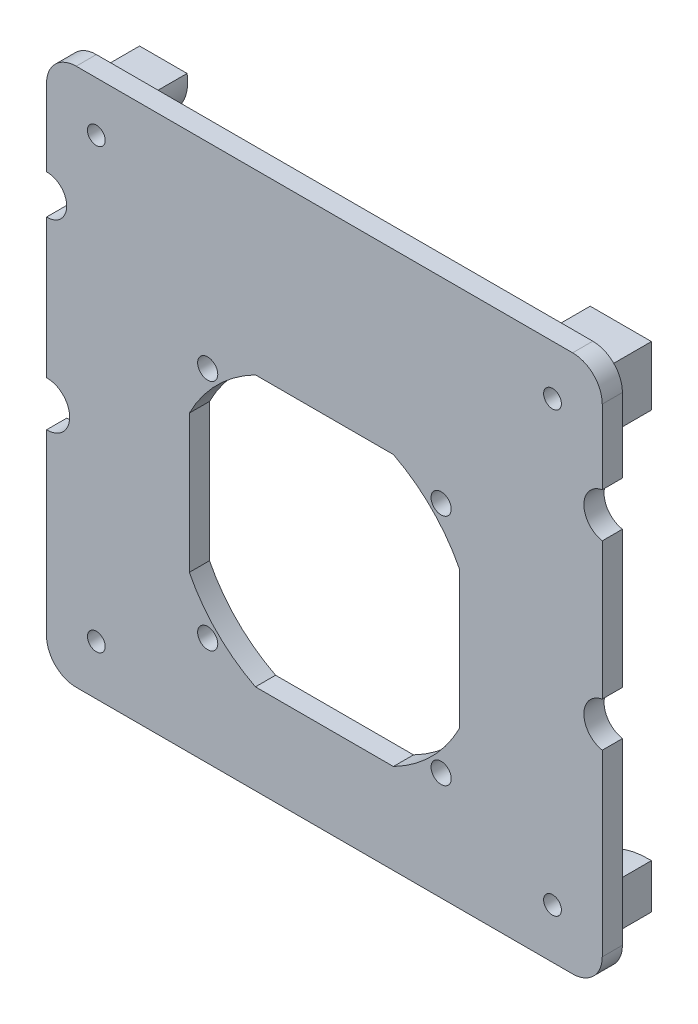
SolidWorks part; units mm, degrees
material "ABS"
ref_plane "Front Plane" through (0, 0, 0) normal (0, 0, 1) x (1, 0, 0)
ref_plane "Top Plane" through (0, 0, 0) normal (0, 1, 0) x (1, 0, 0)
ref_plane "Right Plane" through (0, 0, 0) normal (1, 0, 0) x (0, 0, -1)
sketch "Sketch1" plane through (0, 0, 0) normal (0, 0, 1) x (1, 0, 0)
  line L1 (94.3693, -146.4001) -> (-24.7567, -146.4001)
  line L2 (94.3693, -146.4001) -> (94.3693, -31.0841)
  line L3 (94.3693, -31.0841) -> (-24.7567, -31.0841)
  line L4 (-24.7567, -146.4001) -> (-24.7567, -31.0841)
  circle A0 centre (83.7013, -135.7321) radius 1.905
  circle A2 centre (83.7013, -135.7321) radius 2.54
  circle A3 centre (-14.0887, -135.7321) radius 1.905
  circle A4 centre (-14.0887, -135.7321) radius 2.54
  circle A5 centre (-14.0887, -41.7521) radius 1.905
  circle A6 centre (-14.0887, -41.7521) radius 2.54
  circle A7 centre (83.7013, -41.7521) radius 1.905
  circle A8 centre (83.7013, -41.7521) radius 2.54
extrude "Boss-Extrude1" add sketch "Sketch1" against normal up to surface (10.922 mm away) contours A8 A7 | A6 A5 | A4 A3 | A2 A0 region at (81.2332, -135.7321, 0) region at (-16.5568, -135.7321, 0) region at (-16.5568, -41.7521, 0) region at (81.2332, -41.7521, 0)
sketch "Sketch2" plane through (0, 0, 0) normal (0, 0, 1) x (1, 0, 0)
  line L0 (-6.8751, -142.0821) -> (-20.4387, -142.0821)
  line L1 (-20.4387, -142.0821) -> (-20.4387, -128.5961)
  line L2 (-20.4387, -142.0821) -> (-20.4387, -99.3264) construction
  line L3 (-6.8751, -141.7011) -> (-20.0577, -141.7011)
  line L4 (-20.0577, -141.7011) -> (-20.0577, -128.5961)
  line L5 (-20.4387, -46.0066) -> (-20.4387, -35.4021) construction
  line L6 (-20.4387, -46.0066) -> (-20.4387, -35.4021)
  line L8 (-20.4387, -35.4021) -> (-9.8742, -35.4021)
  line L9 (-20.4387, -35.4021) -> (6.7885, -35.4021) construction
  line L10 (-20.0577, -46.0066) -> (-20.0577, -35.7831)
  line L11 (-20.0577, -35.7831) -> (-9.8742, -35.7831)
  line L12 (73.9223, -142.0821) -> (90.0513, -142.0821)
  line L14 (90.0513, -132.1507) -> (90.0513, -142.0821)
  line L15 (73.9223, -141.7011) -> (89.6703, -141.7011)
  line L17 (90.0513, -48.5085) -> (90.0513, -35.4021)
  line L18 (90.0513, -35.4021) -> (76.5401, -35.4021)
  line L19 (89.6703, -48.5085) -> (89.6703, -35.7831)
  line L20 (89.6703, -35.7831) -> (76.5401, -35.7831)
  line L21 (89.6703, -132.1507) -> (89.6703, -141.7011)
  arc A0 (-6.8751, -141.7011) -> (-20.0577, -128.5961) centre (-30.9159, -152.7015) ccw
  arc A1 (-9.8742, -35.7831) -> (-20.0577, -46.0066) centre (-18.5276, -37.3471) cw
  arc A2 (89.6703, -48.5085) -> (76.5401, -35.7831) centre (98.2455, -26.5239) cw
  arc A6 (73.9223, -141.7011) -> (89.6703, -132.1507) centre (89.0742, -148.9266) cw
  circle A7 centre (83.7013, -135.7321) radius 2.54
  circle A8 centre (83.7013, -41.7521) radius 2.54
  circle A9 centre (-14.0887, -41.7521) radius 2.54
  circle A10 centre (-14.0887, -135.7321) radius 2.54
  circle A11 centre (-14.0887, -135.7321) radius 1.905
  circle A12 centre (83.7013, -135.7321) radius 1.905
  circle A13 centre (83.7013, -41.7521) radius 1.905
  circle A14 centre (-14.0887, -41.7521) radius 1.905
  dimension "D1" = 0.381
  dimension "D2" = 0.381
  dimension "D3" = 0.381
  dimension "D4" = 0.381
extrude "Boss-Extrude3" add sketch "Sketch2" against normal up to surface (10.922 mm away) contours A6 A7 L15 L21 | A7 A12 | A0 A10 L4 L3 | A10 A11 | A1 A9 L11 L10 | A9 A14 | A2 A8 L19 L20 | A8 A13 region at (-11.8104, -134.7827, 0) region at (-13.4664, -141.5152, 0) region at (-16.3708, -40.8119, 0) region at (-19.9114, -40.8948, 0) region at (85.0787, -133.684, 0) region at (77.6816, -136.85, 0) region at (82.7307, -39.4828, 0) region at (85.666, -46.2727, 0)
sketch "Sketch3" plane through (0, 0, 0) normal (0, 0, 1) x (1, 0, 0)
  line L1 (-24.7567, -146.4001) -> (94.3693, -146.4001)
  line L2 (-24.7567, -146.4001) -> (-24.7567, -31.0841)
  line L3 (-24.7567, -31.0841) -> (94.3693, -31.0841)
  line L4 (94.3693, -146.4001) -> (94.3693, -31.0841)
  line L5 (-20.4387, -142.0821) -> (90.0513, -142.0821)
  line L6 (90.0513, -142.0821) -> (90.0513, -35.4021)
  line L7 (-20.4387, -35.4021) -> (90.0513, -35.4021)
  line L8 (-20.4387, -142.0821) -> (-20.4387, -35.4021)
  circle A0 centre (-24.6297, -58.0716) radius 4.191
  circle A1 centre (-24.6297, -96.9336) radius 4.826
  circle A2 centre (95.2583, -96.9336) radius 4.826
  circle A3 centre (95.2583, -58.0716) radius 4.826
  circle A4 centre (-14.0887, -41.7521) radius 1.905
  circle A5 centre (-14.0887, -135.7321) radius 1.905
  circle A6 centre (83.7013, -135.7321) radius 1.905
  circle A7 centre (83.7013, -41.7521) radius 1.905
  circle M1 centre (-14.0887, -135.7321) radius 1.905
  arc M2 (-6.8751, -141.7011) -> (-20.0577, -128.5961) centre (-30.9159, -152.7015) ccw
  line M3 (-20.0577, -128.5961) -> (-20.0577, -141.7011)
  line M4 (-20.0577, -141.7011) -> (-6.8751, -141.7011)
  dimension "D1" = 4.318
extrude "Boss-Extrude4" add sketch "Sketch3" along normal blind 4.318 contours A1 L8 L5 L6 L7 A7 A6 A4 M2 M4 M3 | M4 M2 M3 M1 | A3 L4 L3 L2 A0 L8 L7 L6 L5 A1 L1 A2 | A1 L8 A0 L2 region at (-23.0987, -124.079, 0) region at (-22.5381, -77.0849, 0) region at (35.229, -88.3431, 0) region at (-13.4664, -141.5152, 0)
fillet "Fillet1" radius 6.35 4 edges at (-24.7567, -31.0841, 2.159) (-24.7567, -146.4001, 2.159) (94.3693, -146.4001, 2.159) (94.3693, -31.0841, 2.159)
sketch "Sketch5" plane through (0, 0, 4.318) normal (0, 0, 1) x (1, 0, 0)
  line L0 (34.8063, -146.4001) -> (34.8063, -31.0841)
  line L1 (-18.4067, -146.4001) -> (88.0193, -146.4001) construction
  line L2 (-18.4067, -31.0841) -> (88.0193, -31.0841) construction
  line L3 (-24.7567, -98.1401) -> (94.3693, -98.1401)
  line L6 (-24.7567, -140.0501) -> (-24.7567, -101.7579) construction
  line L7 (94.3693, -140.0501) -> (94.3693, -101.677) construction
  line L9 (5.8503, -69.1841) -> (63.7623, -69.1841)
  line L10 (5.8503, -69.1841) -> (5.8503, -127.0961)
  line L11 (5.8503, -127.0961) -> (63.7623, -127.0961)
  line L12 (63.7623, -69.1841) -> (63.7623, -127.0961)
  line L13 (5.8503, -69.1841) -> (63.7623, -127.0961) construction
  line L14 (5.8503, -127.0961) -> (63.7623, -69.1841) construction
  circle A0 centre (9.7873, -73.1211) radius 2.159
  circle A1 centre (59.8253, -73.1211) radius 2.159
  circle A2 centre (59.8253, -123.1591) radius 2.159
  circle A3 centre (9.7873, -123.1591) radius 2.159
  circle A4 centre (34.8063, -98.1401) radius 32.512 construction
  arc A5 (63.7623, -83.3556) -> (49.5908, -69.1841) centre (34.8063, -98.1401) ccw
  arc A6 (63.7623, -112.9245) -> (49.5908, -127.0961) centre (34.8063, -98.1401) cw
  arc A7 (5.8503, -112.9245) -> (20.0219, -127.0961) centre (34.8063, -98.1401) ccw
  arc A8 (5.8503, -83.3556) -> (20.0219, -69.1841) centre (34.8063, -98.1401) cw
  point P12 (34.8063, -98.1401)
  point P13 (34.8063, -98.1401)
  dimension "D4" = 50.038
  dimension "D5" = 50.038
  dimension "D6" = 50.038
  dimension "D7" = 50.038
  dimension "D1" = 48.26
  dimension "D2" = 57.912
  dimension "D3" = 57.912
extrude "Cut-Extrude1" cut sketch "Sketch5" against normal up to next contours A8 L10 L3 L0 L9 | L12 A5 L9 L0 L3 | A0 | A1 | A2 | A6 L12 L3 L0 L11 | L10 A7 L11 L0 L3 | A3 region at (21.3988, -111.5475, 4.318) region at (48.2138, -111.5475, 4.318) region at (21.3988, -84.7326, 4.318) region at (48.2138, -84.7326, 4.318) region at (9.7873, -73.1211, 4.318) region at (59.8253, -73.1211, 4.318) region at (59.8253, -123.1591, 4.318) region at (9.7873, -123.1591, 4.318)
